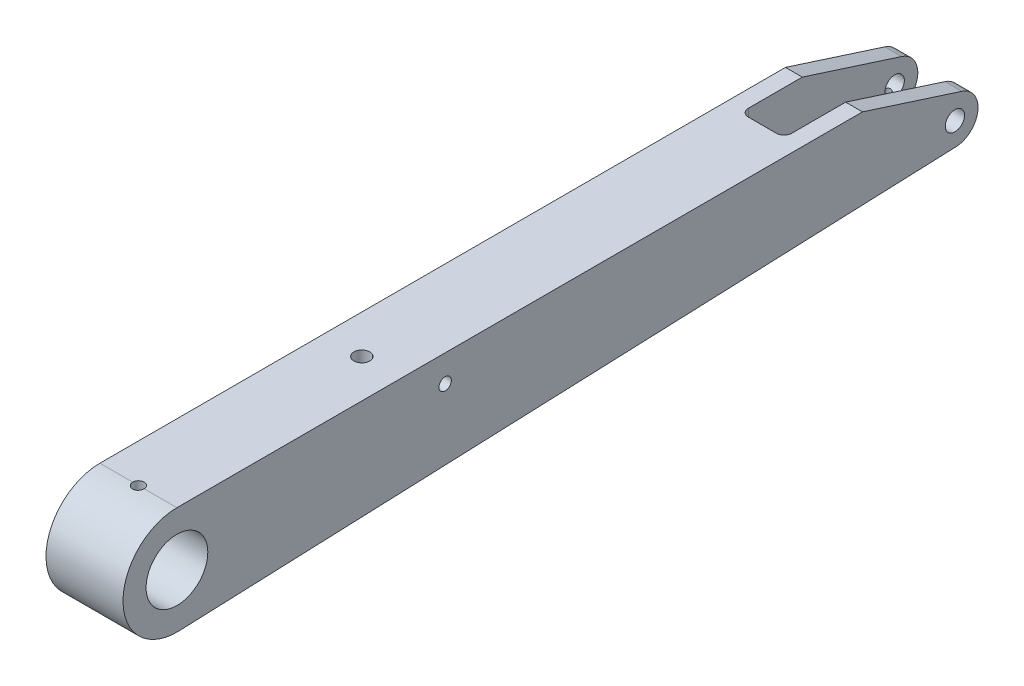
SolidWorks part; units mm, degrees
material "ALUMINUM 6061"
ref_plane "Front" through (0, 0, 0) normal (0, 0, 1) x (1, 0, 0)
ref_plane "Top" through (0, 0, 0) normal (0, 1, 0) x (1, 0, 0)
ref_plane "Right" through (0, 0, 0) normal (1, 0, 0) x (0, 0, -1)
ref_axis "Axis1" through (0, 50, 0) along (0, -1, 0)
ref_plane "Plane2" through (0, -12.7, 0) normal (0, 1, 0) x (-1, 0, 0)
sketch "Sketch1" plane through (0, 0, 0) normal (1, 0, 0) x (0, 0, -1)
  line L0 (0, 22.225) -> (282.575, 22.225)
  line L1 (282.575, 22.225) -> (323.5844, 9.0698)
  line L2 (321.0522, -9.5175) -> (0.8802, -22.2076)
  arc A0 (0, 22.225) -> (0.8802, -22.2076) centre (0, 0) ccw
  arc A1 (321.0522, -9.5175) -> (323.5844, 9.0698) centre (320.675, 0) ccw
  dimension "D1" = 44.45
  dimension "D2" = 19.05
  dimension "D3" = 320.675
  dimension "D4" = 282.575
extrude "BODY" add sketch "Sketch1" along normal mid plane 31.75
sketch "Sketch2" plane through (15.875, 0, 0) normal (1, 0, 0) x (0, 0, -1)
  circle A0 centre (0, 0) radius 12.7254
  dimension "D1" = 25.4508
extrude "1.002 HOLE" cut sketch "Sketch2" against normal through all
sketch "Sketch3" plane through (15.875, 0, 0) normal (1, 0, 0) x (0, 0, -1)
  circle A0 centre (320.675, 0) radius 3.9675
  dimension "D1" = 7.935
extrude ".3124 HOLE" cut sketch "Sketch3" against normal through all
sketch "Sketch4" plane through (0, 0, 0) normal (0, 1, 0) x (1, 0, 0)
  line L0 (15.875, 323.5844) -> (15.875, 282.575) construction
  line L1 (-8.9408, 336.55) -> (8.9408, 336.55)
  line L2 (-8.9408, 336.55) -> (-8.9408, 260.35)
  line L3 (-5.7658, 257.175) -> (5.7658, 257.175)
  line L4 (8.9408, 336.55) -> (8.9408, 260.35)
  arc A0 (-8.9408, 260.35) -> (-5.7658, 257.175) centre (-5.7658, 260.35) ccw
  arc A1 (5.7658, 257.175) -> (8.9408, 260.35) centre (5.7658, 260.35) ccw
  dimension "D1" = 3.175
  dimension "D2" = 257.175
  dimension "D3" = 76.2
  dimension "D4" = 17.8816
  dimension "D5" = 6.9342
extrude "SLOT" cut sketch "Sketch4" against normal mid plane 50.8
sketch "Sketch5" plane through (0, 0, 0) normal (1, 0, 0) x (0, 0, -1)
  line L0 (263.525, -2.5297) -> (234.95, -12.9302)
  line L2 (0.8802, -22.2076) -> (321.0522, -9.5175) construction
  line L3 (234.95, -12.9302) -> (263.525, -11.7976)
  line L4 (263.525, -11.7976) -> (263.525, -2.5297)
  line L5 (282.575, 22.225) -> (0, 22.225) construction
  dimension "D1" = 20
  dimension "D2" = 234.95
  dimension "D3" = 28.575
extrude "ANGULAR CLEARANCE" cut sketch "Sketch5" against normal mid plane 17.8816
sketch "Sketch6" plane through (0, 0, 0) normal (0, 1, 0) x (1, 0, 0)
  circle A0 centre (0, 0) radius 2.3749
  dimension "D1" = 4.7498
extrude "PIN HOLE" cut sketch "Sketch6" against normal mid plane 50.8
hole_wizard "5/16-18 Tapped Hole1" positions "Sketch8" profile "Sketch7" tap size "5/16-18" standard "Ansi Inch" end condition through all
sketch "Sketch8" plane through (0, 22.225, 0) normal (0, 1, 0) x (-1, 0, 0)
  point P0 (0, -92.075)
  dimension "D1" = 92.075
sketch "Sketch7" plane through (0, 22.225, -92.075) normal (1, 0, 0) x (0, 0, 1)
  line L0 (0, 0) -> (0, 44.45)
  line L1 (0, 44.45) -> (3.2639, 44.45)
  line L2 (3.2639, 44.45) -> (3.2639, 0)
  line L5 (3.2639, 0) -> (0, 0)
  line L11 (0, -6.35) -> (0, 107.95) construction
  dimension "Thru Tap Drill Dia." = 6.5278
  dimension "Thru Tap Drill Depth" = 44.45
cosmetic thread "Hole Thread1" parameters "D2"=7.9375
hole_wizard "1/4-20 Tapped Hole1" positions "Sketch10" profile "Sketch9" tap size "1/4-20" standard "Ansi Inch" end condition through all
sketch "Sketch10" plane through (15.875, 0, 0) normal (1, 0, 0) x (0, 0, -1)
  line L0 (0, 0) -> (169.7118, 17.1481) construction
  line L2 (0.8802, -22.2076) -> (321.0522, -9.5175) construction
  circle A0 centre (0, 0) radius 111.125 construction
  point P0 (110.562, 11.1715)
  dimension "D1" = 222.25
  dimension "D2" = 3.5
sketch "Sketch9" plane through (15.875, 11.1715, -110.562) normal (0, 1, 0) x (0, 0, -1)
  line L0 (0, 0) -> (0, 31.75)
  line L1 (0, 31.75) -> (2.5527, 31.75)
  line L2 (2.5527, 31.75) -> (2.5527, 0)
  line L5 (2.5527, 0) -> (0, 0)
  line L11 (0, -6.35) -> (0, 107.95) construction
  dimension "Thru Tap Drill Dia." = 5.1054
  dimension "Thru Tap Drill Depth" = 31.75
cosmetic thread "Hole Thread2" parameters "D2"=6.35
hole_wizard "#8-32 Tapped Hole1" positions "Sketch13" profile "Sketch12" tap size "#8-32" standard "Ansi Inch" end condition up to next
sketch "Sketch13" plane through (0, -12.7, 0) normal (0, 1, 0) x (-1, 0, 0)
  line L0 (15.875, -0.8802) -> (15.875, -321.0522) construction
  point P0 (12.3952, -320.675)
  dimension "D1" = 3.4798
  dimension "D2" = 320.675
sketch "Sketch12" plane through (-12.3952, -12.7, -320.675) normal (1, 0, 0) x (0, 0, -1)
  line L0 (0, 0) -> (0, 8.7325)
  line L1 (0, 8.7325) -> (1.7272, 8.7325)
  line L2 (1.7272, 8.7325) -> (1.7272, 0)
  line L5 (1.7272, 0) -> (0, 0)
  line L11 (0, -6.35) -> (0, 107.95) construction
  dimension "Thru Tap Drill Dia." = 3.4544
  dimension "Thru Tap Drill Depth" = 8.7325
cosmetic thread "Hole Thread4" parameters "D2"=4.1656
